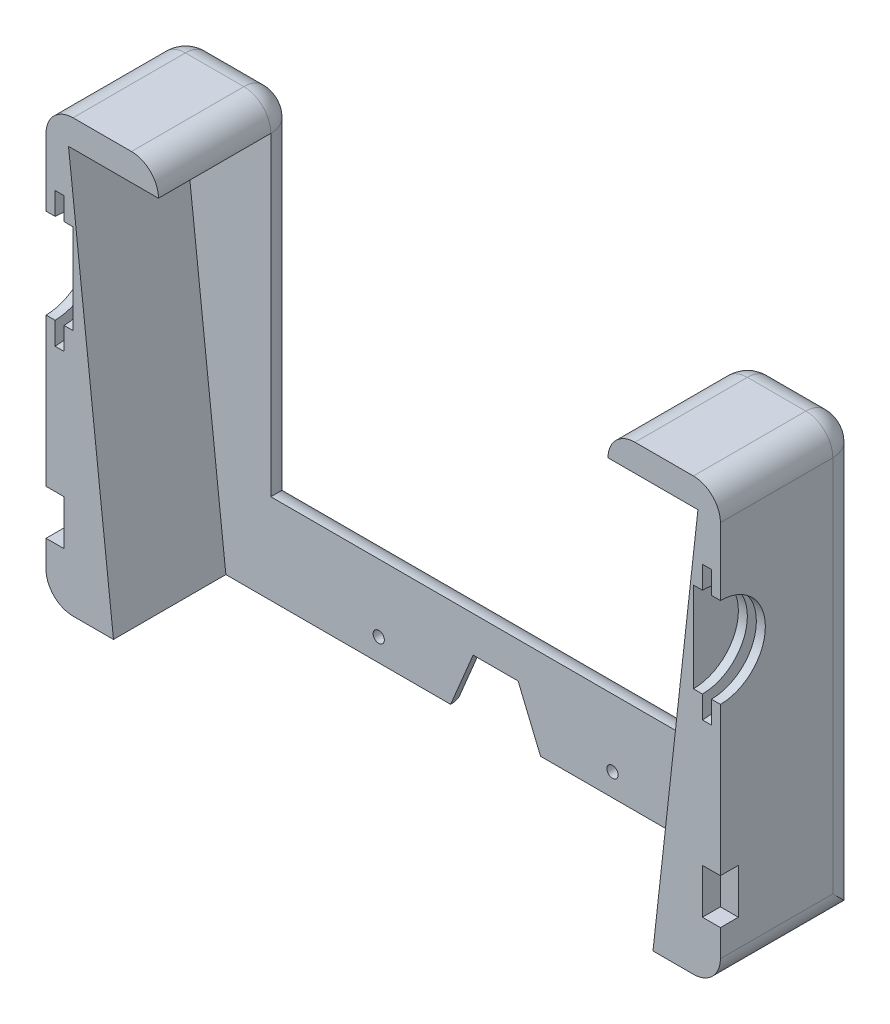
SolidWorks part; units mm, degrees
ref_plane "Front Plane" through (0, 0, 0) normal (0, 0, 1) x (1, 0, 0)
ref_plane "Top Plane" through (0, 0, 0) normal (0, 1, 0) x (1, 0, 0)
ref_plane "Right Plane" through (0, 0, 0) normal (1, 0, 0) x (0, 0, -1)
sketch "Sketch1" plane through (0, 0, 0) normal (0, 0, 1) x (1, 0, 0)
  line L1 (-37.5, 25.5) -> (37.5, 25.5)
  line L2 (-37.5, 25.5) -> (-37.5, -22.5)
  line L3 (-37.5, -22.5) -> (37.5, -22.5)
  line L4 (37.5, 25.5) -> (37.5, -22.5)
  dimension "D1" = 75
  dimension "D2" = 48
  dimension "D3" = 37.5
  dimension "D4" = 25.5
extrude "Boss-Extrude1" add sketch "Sketch1" along normal mid plane 15.5
sketch "Sketch2" plane through (0, 0, 7.75) normal (0, 0, 1) x (1, 0, 0)
  line L0 (-35, 22.5) -> (35, 22.5)
  line L1 (-30, -22.5) -> (30, -22.5)
  line L2 (-37.5, -22.5) -> (37.5, -22.5) construction
  line L3 (-35, 22.5) -> (-30, -22.5)
  line L4 (35, 22.5) -> (30, -22.5)
  dimension "D1" = 70
  dimension "D2" = 60
  dimension "D3" = 45
  dimension "D4" = 2.5
  dimension "D5" = 7.5
extrude "Cut-Extrude1" cut sketch "Sketch2" against normal blind 12.5
sketch "Sketch3" plane through (0, 0, -7.75) normal (0, 0, -1) x (-1, 0, 0)
  line L0 (-37.5, 25.5) -> (37.5, 25.5) construction
  line L1 (-25, 25.5) -> (25, 25.5)
  line L2 (-25, 25.5) -> (-25, -12.5)
  line L3 (-25, -12.5) -> (25, -12.5)
  line L4 (25, 25.5) -> (25, -12.5)
  dimension "D1" = 50
  dimension "D2" = 38
  dimension "D3" = 12.5
extrude "Cut-Extrude2" cut sketch "Sketch3" against normal through all
sketch "Sketch4" plane through (0, 0, 0) normal (0, 0, 1) x (1, 0, 0)
  line L0 (-37.5, -22.5) -> (37.5, -22.5) construction
  line L1 (0, 0) -> (0, -37.0073) construction
  line L2 (2.5, -16.5) -> (5, -22.5)
  line L3 (-2.5, -16.5) -> (-5, -22.5)
  line L4 (2.5, -16.5) -> (-2.5, -16.5)
  line L5 (5, -22.5) -> (-5, -22.5)
  circle A0 centre (-13, -20) radius 0.625
  circle A1 centre (13, -20) radius 0.625
  dimension "D1" = 1.25
  dimension "D2" = 13
  dimension "D3" = 2.5
  dimension "D4" = 5
  dimension "D5" = 10
  dimension "D6" = 2.5
  dimension "D7" = 5
  dimension "D8" = 6
extrude "Cut-Extrude3" cut sketch "Sketch4" against normal blind 12.5
fillet "Fillet1" radius 3 16 edges at (-3.75, -19.5, -7.75) (3.75, -19.5, -7.75) (0, -16.5, -7.75) (0, -12.5, -7.75) (37.5, 25.5, 0) (31.25, 25.5, -7.75) (25, 25.5, 0) (-25, 25.5, 0) (-37.5, 25.5, 0) (-31.25, 25.5, -7.75) (-37.5, 1.5, -7.75) (-25, 6.5, -7.75) (25, 6.5, -7.75) (37.5, 1.5, -7.75) (-37.5, -22.5, 0) (37.5, -22.5, 0)
sketch "Sketch7" plane through (0, 0, -7.75) normal (0, 0, -1) x (-1, 0, 0)
  line L0 (0, 0) -> (0, -28.4917) construction
  circle A0 centre (-13, -20) radius 1.25
  circle A1 centre (13, -20) radius 1.25
  dimension "D1" = 2.5
extrude "Cut-Extrude4" cut sketch "Sketch7" against normal blind 1
sketch "Sketch8" plane through (0, 0, 7.75) normal (0, 0, 1) x (1, 0, 0)
  line L0 (0, 20.9696) -> (0, -29.4783) construction
  line L2 (-37.5, 22.5) -> (-37.5, -19.5) construction
  line L3 (-37.5, -11.5) -> (-35.5, -11.5)
  line L4 (-37.5, -11.5) -> (-37.5, -16.5)
  line L5 (-37.5, -16.5) -> (-35.5, -16.5)
  line L6 (-35.5, -11.5) -> (-35.5, -16.5)
  line L11 (37.5, -16.5) -> (35.5, -16.5)
  line L12 (35.5, -11.5) -> (35.5, -16.5)
  line L13 (37.5, -11.5) -> (35.5, -11.5)
  line L14 (37.5, -11.5) -> (37.5, -16.5)
  dimension "D1" = 5
  dimension "D2" = 2
  dimension "D3" = 3
extrude "Cut-Extrude5" cut sketch "Sketch8" against normal blind 2
sketch "Sketch9" plane through (-37.5, 0, 0) normal (-1, 0, 0) x (0, 0, 1)
  line L0 (7.75, 22.5) -> (7.75, -11.5) construction
  circle A0 centre (7.75, 10) radius 5
  dimension "D1" = 10
  dimension "D2" = 10
extrude "Cut-Extrude6" cut sketch "Sketch9" against normal blind 3
ref_plane "Plane1" through (-36, 0, 0) normal (-1, 0, 0) x (0, 0, 1)
sketch "Sketch10" plane through (-36, 0, 0) normal (-1, 0, 0) x (0, 0, 1)
  line L0 (7.75, 15) -> (7.75, 5) construction
  circle A0 centre (7.75, 10) radius 7.5
  dimension "D1" = 15
extrude "Cut-Extrude7" cut sketch "Sketch10" against normal mid plane 1
mirror "Mirror1" about plane through (0, 0, 0) normal (1, 0, 0) of "Cut-Extrude7", "Cut-Extrude6"
